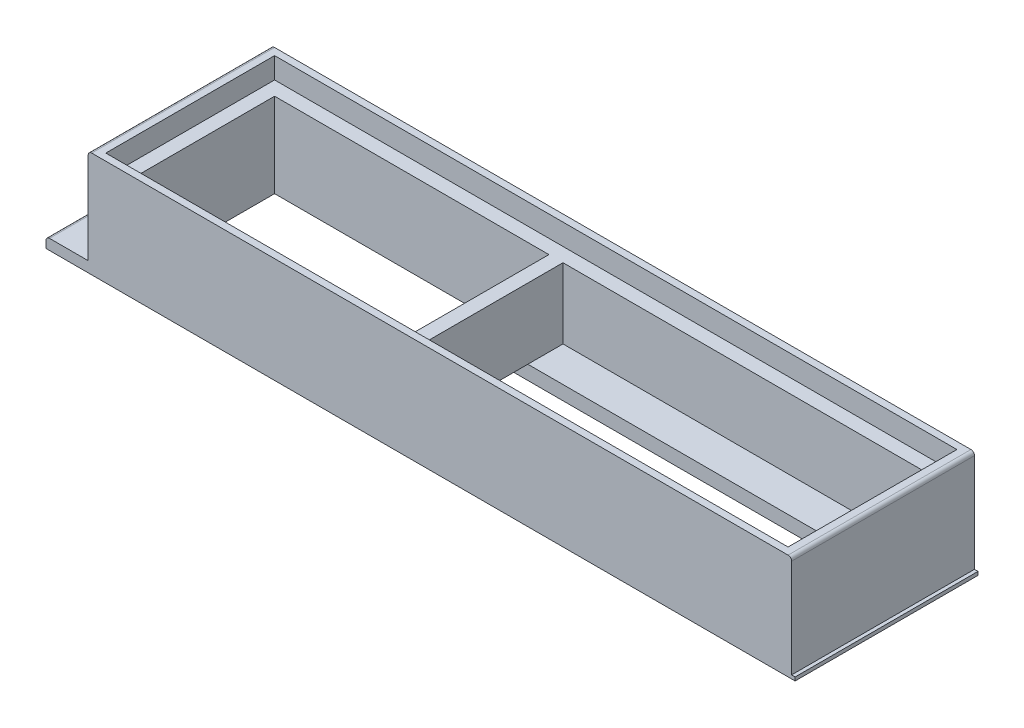
SolidWorks part; units mm, degrees
material "ABS"
ref_plane "Front Plane" through (0, 0, 0) normal (0, 0, 1) x (1, 0, 0)
ref_plane "Top Plane" through (0, 0, 0) normal (0, 1, 0) x (1, 0, 0)
ref_plane "Right Plane" through (0, 0, 0) normal (1, 0, 0) x (0, 0, -1)
sketch "Sketch1" plane through (0, 0, 0) normal (0, 1, 0) x (1, 0, 0)
  line L1 (0, 0) -> (107, 0)
  line L2 (0, 0) -> (0, -26)
  line L3 (0, -26) -> (107, -26)
  line L4 (107, 0) -> (107, -26)
  dimension "D1" = 107
  dimension "D2" = 26
extrude "Boss-Extrude1" add sketch "Sketch1" along normal blind 15 contours L2 L3 L4 L1
sketch "Sketch2" plane through (0, 0, 26) normal (0, 0, 1) x (1, 0, 0)
  line L0 (0, 0) -> (107, 0) construction
  line L1 (107, 15) -> (106, 15)
  line L2 (107, 15) -> (107, 0.5)
  line L3 (107, 0.5) -> (106, 0.5)
  line L4 (106, 15) -> (106, 0.5)
  line L6 (0, 15) -> (6, 15)
  line L7 (0, 15) -> (0, 1.5)
  line L8 (0, 1.5) -> (6, 1.5)
  line L9 (6, 15) -> (6, 1.5)
  dimension "D1" = 1
  dimension "D2" = 0.5
  dimension "D3" = 6
  dimension "D4" = 1.5
extrude "Cut-Extrude1" cut sketch "Sketch2" against normal through all
fillet "Fillet1" radius 0.5 3 edges at (6, 15, 13) (0, 1.5, 13) (106, 15, 13)
sketch "Sketch14" plane through (0, 15, 0) normal (0, 1, 0) x (1, 0, 0)
  line L14 (104.5, -25) -> (104.5, -1)
  line L15 (7.5, -1) -> (7.5, -25)
  line L16 (7.5, -25) -> (104.5, -25)
  line L17 (104.5, -1) -> (7.5, -1)
  line L18 (104.5, -25) -> (104.5, -1)
  line L19 (7.5, -1) -> (7.5, -25)
  line L20 (7.5, -25) -> (104.5, -25)
  line L21 (104.5, -1) -> (7.5, -1)
  dimension "D1" = 1
hole_wizard "CSK for M2 Countersunk Flat Head Screw1" positions "3DSketch1" profile "Sketch16" countersink size "M2" standard "ISO"
sketch3d "3DSketch1"
  point P0 (3, 1.5, 13)
  dimension "D1" = 3
  dimension "D2" = 13
sketch "Sketch16" plane through (3, 1.5, 13) normal (1, 0, 0) x (0, 0, 1)
  line L0 (0, 0) -> (0, 15.721)
  line L1 (0, 15.721) -> (1.2, 15)
  line L2 (1.2, 15) -> (1.2, 1)
  line L3 (1.2, 1) -> (2.2, 0)
  line L5 (2.2, 0) -> (0, 0)
  line L6 (-1.2, 1) -> (-2.2, 0) construction
  line L10 (0, 15.721) -> (-1.2, 15) construction
  line L11 (0, -6.35) -> (0, 107.95) construction
  dimension "Hole Dia." = 2.4
  dimension "Hole Depth" = 15
  dimension "Near C'Sink Dia." = 4.4
  dimension "Near C'Sink Angle" = 90
  dimension "Drill Angle" = 118
extrude "Cut-Extrude7" cut sketch "Sketch14" against normal through all
extrude "Boss-Extrude3" add sketch "Sketch14<3>" against normal blind 1
sketch "Sketch14<3>" plane through (0, 15, 0) normal (0, 1, 0) x (1, 0, 0) same geometry as "Sketch14"
sketch "Sketch18" plane through (0, 0, 0) normal (0, 1, 0) x (1, 0, 0)
  line L1 (7.5, -1) -> (104.5, -1)
  line L2 (7.5, -1) -> (7.5, -25)
  line L3 (7.5, -25) -> (104.5, -25)
  line L4 (104.5, -1) -> (104.5, -25)
extrude "Cut-Extrude8" cut sketch "Sketch18" along normal through all
sketch "Sketch20" plane through (0, 15, 0) normal (0, 1, 0) x (1, 0, 0)
  line L11 (7.5, -1) -> (104.5, -1)
  line L12 (7.5, -1) -> (7.5, -25)
  line L13 (7.5, -25) -> (104.5, -25)
  line L14 (102.5, -23) -> (102.5, -3)
  line L15 (9.5, -23) -> (102.5, -23)
  line L16 (9.5, -3) -> (9.5, -23)
  line L17 (102.5, -3) -> (9.5, -3)
  line L18 (102.5, -23) -> (102.5, -3)
  line L19 (9.5, -23) -> (102.5, -23)
  line L20 (9.5, -3) -> (9.5, -23)
  line L21 (102.5, -3) -> (9.5, -3)
  line L22 (104.5, -1) -> (104.5, -25)
  dimension "D1" = 2
extrude "Boss-Extrude4" add sketch "Sketch20" against normal up to surface (15 mm away) up to face at (56, 0, 13)
extrude "Cut-Extrude9" cut sketch "Sketch20<2>" against normal blind 3
sketch "Sketch20<2>" plane through (0, 15, 0) normal (0, 1, 0) x (1, 0, 0) same geometry as "Sketch20"
sketch "Sketch21" plane through (0, 0, 3) normal (0, 0, 1) x (1, 0, 0)
  line L1 (102.5, 0) -> (50.5, 0)
  line L2 (102.5, 0) -> (102.5, 2)
  line L3 (102.5, 2) -> (50.5, 2)
  line L4 (50.5, 0) -> (50.5, 2)
  dimension "D1" = 52
  dimension "D2" = 2
extrude "Boss-Extrude5" add sketch "Sketch21" along normal blind 5
sketch "Sketch22" plane through (0, 0, 23) normal (0, 0, -1) x (-1, 0, 0)
  line L1 (-102.5, 0) -> (-50.5, 0)
  line L2 (-102.5, 0) -> (-102.5, 2)
  line L3 (-102.5, 2) -> (-50.5, 2)
  line L4 (-50.5, 0) -> (-50.5, 2)
  dimension "D1" = 52
  dimension "D2" = 2
extrude "Boss-Extrude6" add sketch "Sketch22" along normal blind 5
sketch "Sketch23" plane through (0, 0, 26) normal (0, 0, 1) x (1, 0, 0)
  line L1 (107, 0) -> (106.5, 0)
  line L2 (107, 0) -> (107, 16.6122)
  line L3 (107, 16.6122) -> (106.5, 16.6122)
  line L4 (106.5, 0) -> (106.5, 16.6122)
  dimension "D1" = 0.5
extrude "Cut-Extrude10" cut sketch "Sketch23" against normal through all
sketch "Sketch25" plane through (0, 0, 23) normal (0, 0, -1) x (-1, 0, 0)
  line L0 (-9.5, 12) -> (-102.5, 12) construction
  line L1 (-50.5, 0) -> (-48.5, 0)
  line L2 (-50.5, 0) -> (-50.5, 12)
  line L3 (-50.5, 12) -> (-48.5, 12)
  line L4 (-48.5, 0) -> (-48.5, 12)
  dimension "D1" = 2
extrude "Boss-Extrude7" add sketch "Sketch25" along normal up to next
sketch "Sketch26" plane through (50.5, 0, 0) normal (1, 0, 0) x (0, 0, -1)
  line L0 (-8, 2) -> (-3, 2) construction
  line L1 (-18, 0) -> (-8, 0)
  line L2 (-18, 0) -> (-18, 2)
  line L3 (-18, 2) -> (-8, 2)
  line L4 (-8, 0) -> (-8, 2)
extrude "Cut-Extrude11" cut sketch "Sketch26" against normal up to next
